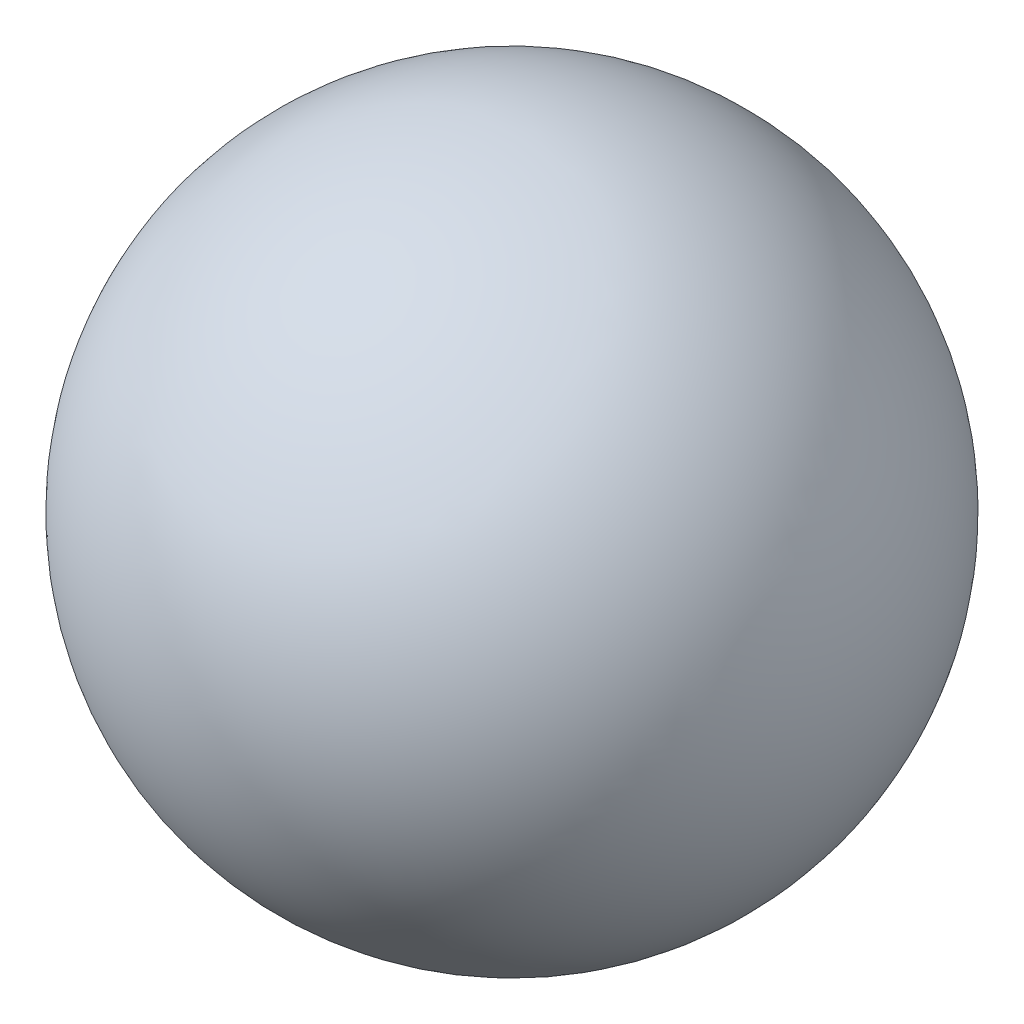
SolidWorks part; units mm, degrees
material "Rubber"
ref_plane "Front Plane" through (0, 0, 0) normal (0, 0, 1) x (1, 0, 0)
ref_plane "Top Plane" through (0, 0, 0) normal (0, 1, 0) x (1, 0, 0)
ref_plane "Right Plane" through (0, 0, 0) normal (1, 0, 0) x (0, 0, -1)
sketch "Sketch1" plane through (0, 0, 0) normal (0, 0, 1) x (1, 0, 0)
  line L2 (-75, 0) -> (75, 0)
  arc A2 (-75, 0) -> (75, 0) centre (0, 0) cw
revolve "Revolve4" add sketch "Sketch1" angle 360 about L2
